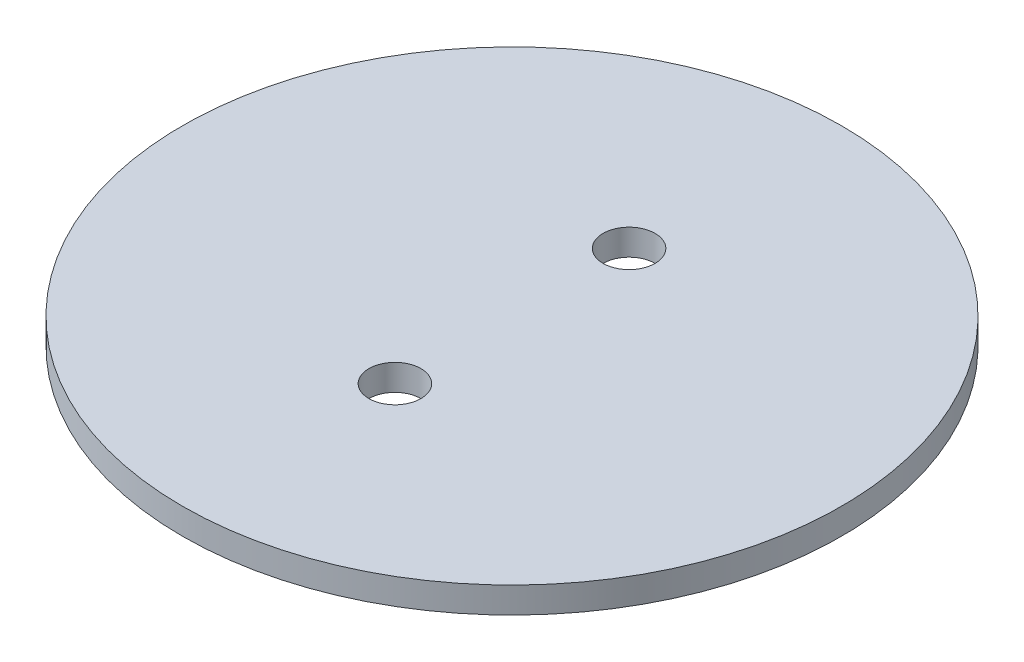
SolidWorks part; units mm, degrees
ref_plane "Front Plane" through (0, 0, 0) normal (0, 0, 1) x (1, 0, 0)
ref_plane "Top Plane" through (0, 0, 0) normal (0, 1, 0) x (1, 0, 0)
ref_plane "Right Plane" through (0, 0, 0) normal (1, 0, 0) x (0, 0, -1)
sketch "Sketch1" plane through (0, 0, 0) normal (0, 1, 0) x (1, 0, 0)
  line L0 (-28.5, 0) -> (28.5, 0) construction
  line L1 (0, 0) -> (0, 13.5)
  line L2 (0, 0) -> (0, -13.5)
  circle A0 centre (0, 0) radius 38
  circle A1 centre (28.5, 0) radius 3 construction
  circle A2 centre (-28.5, 0) radius 3 construction
  circle A3 centre (0, 13.5) radius 3
  circle A4 centre (0, -13.5) radius 3
  circle A5 centre (-28.5, 0) radius 6.25 construction
  circle A6 centre (0, 13.5) radius 12.5 construction
  circle A7 centre (0, -13.5) radius 12.5 construction
  circle A8 centre (28.5, 0) radius 6.25 construction
  point P11 (0, 0)
  dimension "D1" = 76
  dimension "D3" = 6
  dimension "D4" = 13.5
  dimension "D5" = 6
  dimension "D6" = 12.5
  dimension "D7" = 25
  dimension "D2" = 57
extrude "Boss-Extrude1" add sketch "Sketch1" against normal blind 3 contours A0 A4 A3 A2 A1 region at (-36.9252, 0, 0)
